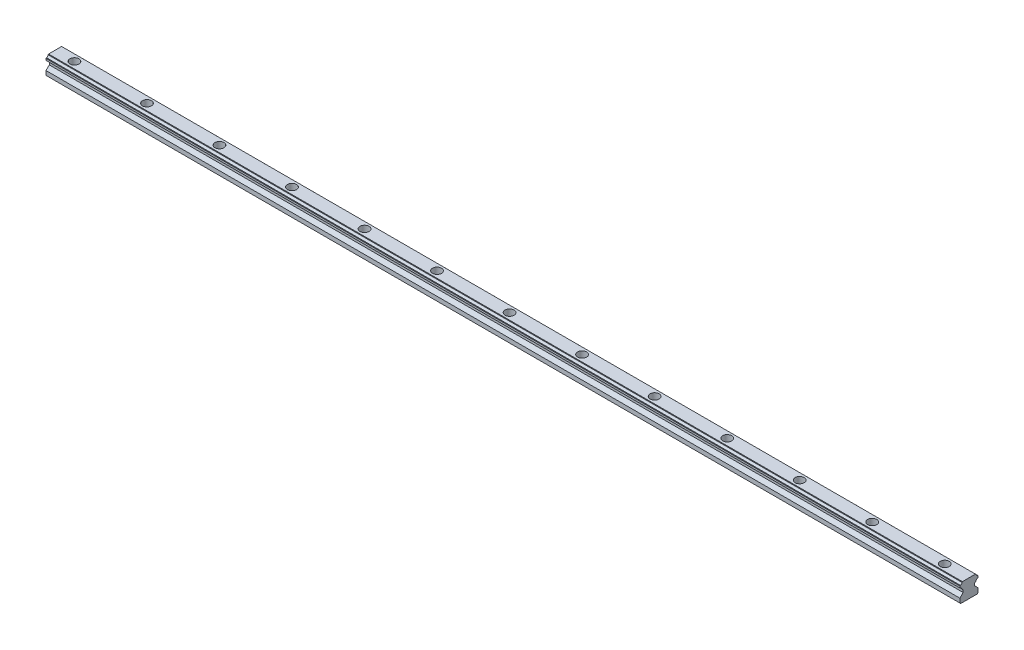
SolidWorks part; units mm, degrees
ref_plane "Front Plane" through (0, 0, 0) normal (0, 0, 1) x (1, 0, 0)
ref_plane "Top Plane" through (0, 0, 0) normal (0, 1, 0) x (1, 0, 0)
ref_plane "Right Plane" through (0, 0, 0) normal (1, 0, 0) x (0, 0, -1)
ref_plane "Plane1" through (0, 15, 0) normal (0, 1, 0) x (-1, 0, 0)
sketch "Sketch1" plane through (0, 15, 0) normal (0, 1, 0) x (-1, 0, 0)
  line L0 (616, -7.5) -> (616, 7.5)
  line L1 (616, 7.5) -> (-140, 7.5)
  line L2 (-140, 7.5) -> (-140, -7.5)
  line L3 (-140, -7.5) -> (616, -7.5)
  dimension "D1" = 756
extrude "Boss-Extrude1" add sketch "Sketch1" against normal blind 15
sketch "Sketch2" plane through (-616, 0, 0) normal (-1, 0, 0) x (0, 0, 1)
  line L0 (-7.5, 11.1352) -> (-7.5, 4.2)
  line L1 (-7.5, 4.2) -> (-4.8, 4.2)
  line L2 (-4.8, 4.2) -> (-4.8, 8.84)
  line L3 (-4.8, 8.84) -> (-5.7542, 9.7942)
  arc A0 (-5.7542, 9.7942) -> (-7.5, 11.1352) centre (-7.3005, 9.588) ccw
extrude "Cut-Extrude1" cut sketch "Sketch2" against normal through all
sketch "Sketch3" plane through (-616, 0, 0) normal (-1, 0, 0) x (0, 0, 1)
  line L0 (7.5, 4.2) -> (7.5, 11.1352)
  line L1 (5.7542, 9.7942) -> (4.8, 8.84)
  line L2 (4.8, 8.84) -> (4.8, 4.2)
  line L3 (4.8, 4.2) -> (7.5, 4.2)
  arc A0 (7.5, 11.1352) -> (5.7542, 9.7942) centre (7.3005, 9.588) ccw
extrude "Cut-Extrude2" cut sketch "Sketch3" against normal through all
draft "Draft1" type of draft neutral plane draft angle 45 faces to draft 1 face at (-238, 4.2, -6.15) neutral plane through (140, 0, -7.5) neutral plane normal (0, 0, -1) parameters "D1"=45
draft "Draft2" type of draft neutral plane draft angle 45 faces to draft 1 face at (-238, 4.2, 6.15) neutral plane through (-616, 0, 7.5) neutral plane normal (0, 0, 1) parameters "D1"=45
hole_wizard "Hole1" positions "Sketch5" profile "Sketch4" legacy
sketch "Sketch5" plane through (-616, 0, 0) normal (-1, 0, 0) x (0, 0, 1)
  point P0 (-7.3005, 14.813)
  point P1 (7.3005, 14.813)
sketch "Sketch4" plane through (-616, 14.813, -7.3005) normal (0, 1, 0) x (0, 0, 1)
  line L0 (0, 0) -> (0, 756)
  line L1 (0, 756) -> (1.56, 756)
  line L2 (1.56, 756) -> (1.56, 0)
  line L3 (1.56, 0) -> (0, 0)
  line L4 (0, 110) -> (0, -10) construction
  dimension "Diameter" = 3.12
  dimension "Depth" = 756
hole_wizard "CBORE for M4 Hex Head Machine Screw1" positions "Sketch7" profile "Sketch6" counterbore size "M4" standard "Ansi Metric" end condition through all
sketch "Sketch7" plane through (0, 15, 0) normal (0, 1, 0) x (-1, 0, 0)
  point P0 (-60, 0)
  point P1 (-120, 0)
  point P2 (0, 0)
  point P12 (60, 0)
  point P21 (120, 0)
  point P22 (180, 0)
  point P23 (240, 0)
  point P24 (300, 0)
  point P25 (360, 0)
  point P26 (420, 0)
  point P27 (480, 0)
  point P28 (540, 0)
  point P29 (600, 0)
  dimension "D1" = 120
  dimension "D2" = 60
  dimension "D3" = 10
sketch "Sketch6" plane through (60, 15, 0) normal (1, 0, 0) x (0, 0, 1)
  line L0 (0, 0) -> (0, 15)
  line L1 (0, 15) -> (2.25, 15)
  line L3 (2.25, 15) -> (2.25, 5.3)
  line L4 (2.25, 5.3) -> (3.75, 5.3)
  line L5 (3.75, 5.3) -> (3.75, 0)
  line L7 (3.75, 0) -> (0, 0)
  line L11 (0, -6.35) -> (0, 107.95) construction
  dimension "Thru Hole Dia." = 4.5
  dimension "Thru Hole Depth" = 15
  dimension "C'Bore Dia." = 7.5
  dimension "C'Bore Depth" = 5.3
chamfer "Chamfer1" distance 0.3591 angle 45 2 edges at (-238, 13.2658, -7.5) (-238, 13.2658, 7.5) first distance on face at (-238, 12.2005, -7.5) first distance on face at (-238, 12.2005, 7.5)
chamfer "Chamfer2" distance 0.3516 angle 45 2 edges at (-238, 11.1352, 7.5) (-238, 11.1352, -7.5) first distance on face at (-238, 10.6449, 6.4887) first distance on face at (-238, 12.0209, -7.5)
chamfer "Chamfer3" distance 0.3484 angle 45.001 2 edges at (-238, 15, 5.7518) (-238, 15, -5.7518) first distance on face at (60, 15, 3.75)
chamfer "Chamfer4" distance 0.7 angle 45 1 edges at (-238, 0, 7.5) first distance on face at (60, 0, 2.25)
chamfer "Chamfer5" distance 0.7 angle 45 1 edges at (-238, 0, -7.5) first distance on face at (-238, 2.1, -7.5)
